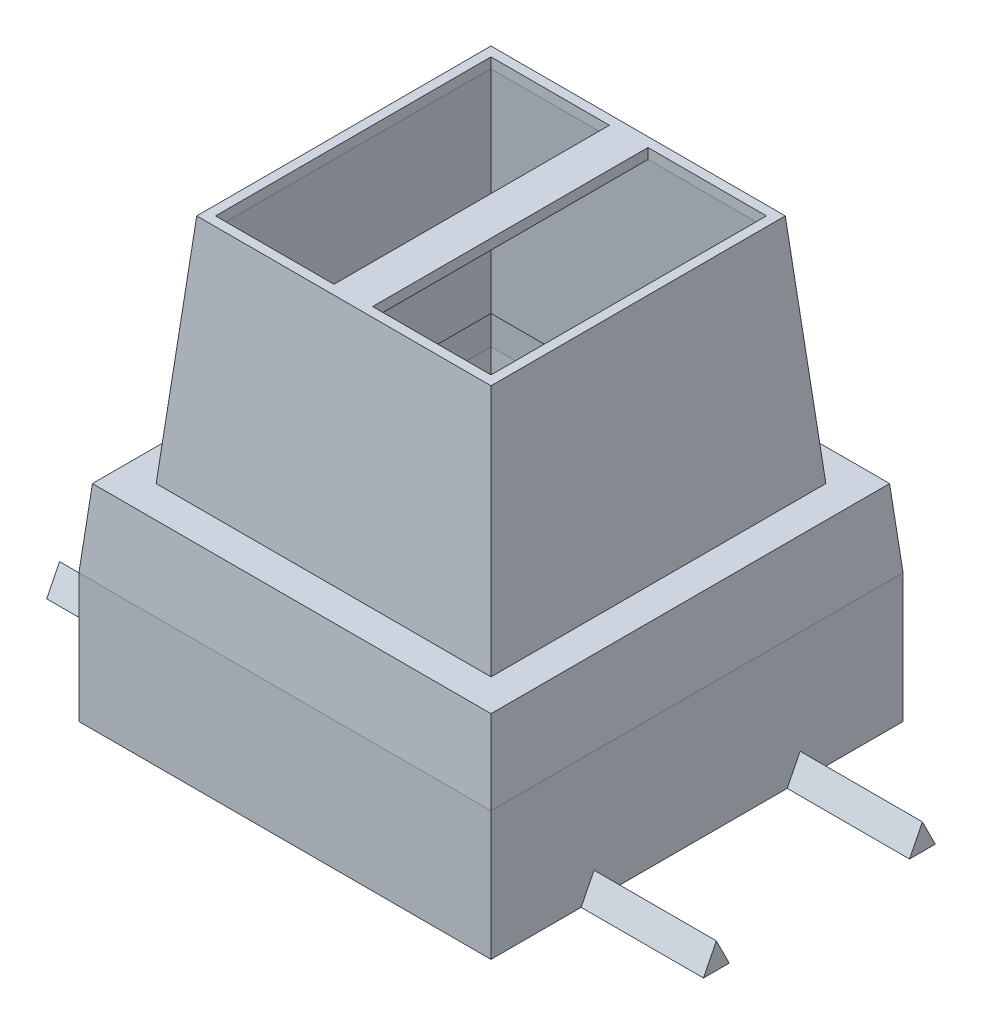
SolidWorks part; units mm, degrees
ref_plane "Front Plane" through (0, 0, 0) normal (0, 0, 1) x (1, 0, 0)
ref_plane "Top Plane" through (0, 0, 0) normal (0, 1, 0) x (1, 0, 0)
ref_plane "Right Plane" through (0, 0, 0) normal (1, 0, 0) x (0, 0, -1)
sketch "Sketch1" plane through (0, 0, 0) normal (0, 1, 0) x (1, 0, 0)
  line L13 (0, 0) -> (-32, 0)
  line L14 (0, 0) -> (0, 32)
  line L15 (0, 32) -> (-32, 32)
  line L16 (-32, 0) -> (-32, 32)
  dimension "D1" = 32
  dimension "D2" = 32
extrude "Boss-Extrude1" add sketch "Sketch1" along normal blind 6 draft 5
sketch "Sketch2" plane through (0, 6, 0) normal (0, 1, 0) x (1, 0, 0)
  line L0 (-31.4751, 0.5249) -> (-0.5249, 0.5249) construction
  line L1 (-29, 29) -> (-3, 29)
  line L2 (-29, 29) -> (-29, 3)
  line L3 (-29, 3) -> (-3, 3)
  line L4 (-3, 29) -> (-3, 3)
  line L5 (-0.5249, 0.5249) -> (-0.5249, 31.4751) construction
  point P5 (-16, 3)
  point P8 (-16, 0.5249)
  point P9 (-3, 16)
  point P12 (-0.5249, 16)
  dimension "D1" = 26
  dimension "D2" = 26
extrude "Boss-Extrude2" add sketch "Sketch2" along normal blind 18 draft 5
shell "Shell1" thickness 0.8 removed face at (-16, 0, -16)
chamfer "Chamfer1" distance 2.5 angle 45 4 edges at (-16, 5.2, -1.258) (-30.742, 5.2, -16) (-16, 5.2, -30.742) (-1.258, 5.2, -16) first distance on face at (-16, 5.2, -16)
sketch "Sketch3" plane through (0, 23.2, 0) normal (0, -1, 0) x (1, 0, 0)
  line L0 (-5.3079, -26.6921) -> (-26.6921, -26.6921) construction
  line L1 (-17.5, -5.3079) -> (-14.5, -5.3079)
  line L2 (-17.5, -5.3079) -> (-17.5, -26.6921)
  line L3 (-17.5, -26.6921) -> (-14.5, -26.6921)
  line L4 (-14.5, -5.3079) -> (-14.5, -26.6921)
  line L5 (-26.6921, -5.3079) -> (-5.3079, -5.3079) construction
  line L7 (-17.5, -5.3079) -> (-26.6921, -5.3079)
  line L8 (-17.5, -5.3079) -> (-17.5, -26.6921)
  line L9 (-17.5, -26.6921) -> (-26.6921, -26.6921)
  line L10 (-26.6921, -5.3079) -> (-26.6921, -26.6921)
  line L11 (-14.5, -5.3079) -> (-5.3079, -5.3079)
  line L12 (-14.5, -5.3079) -> (-14.5, -26.6921)
  line L13 (-14.5, -26.6921) -> (-5.3079, -26.6921)
  line L14 (-5.3079, -5.3079) -> (-5.3079, -26.6921)
  point P6 (-16, -5.3079)
  point P9 (-16, -5.3079)
  line M13 (-26.6921, -5.3079) -> (-26.6921, -26.6921)
  line M14 (-26.6921, -26.6921) -> (-5.3079, -26.6921)
  line M15 (-5.3079, -26.6921) -> (-5.3079, -5.3079)
  line M16 (-5.3079, -5.3079) -> (-26.6921, -5.3079)
  dimension "D1" = 3
extrude "Cut-Extrude1" cut sketch "Sketch3" against normal through all contours L2 M16 M13 M14 | L4 M16 M14 M15 region at (-22.0961, 23.2, -16) region at (-9.9039, 23.2, -16)
sketch "Sketch4" plane through (0, 0, 0) normal (0, -1, 0) x (1, 0, 0)
  line L1 (-32, 0) -> (0, 0)
  line L2 (-32, 0) -> (-32, -32)
  line L3 (-32, -32) -> (0, -32)
  line L4 (0, 0) -> (0, -32)
  line L5 (-0.8031, -31.1969) -> (-31.1969, -31.1969)
  line L6 (-0.8031, -31.1969) -> (-0.8031, -0.8031)
  line L7 (-0.8031, -0.8031) -> (-31.1969, -0.8031)
  line L8 (-31.1969, -31.1969) -> (-31.1969, -0.8031)
extrude "Boss-Extrude3" add sketch "Sketch4" along normal blind 10
sketch "Sketch5" plane through (-32, 0, 0) normal (-1, 0, 0) x (0, 0, 1)
  line L0 (-25, -10) -> (-23, -10)
  line L1 (0, -10) -> (-32, -10) construction
  line L2 (-23, -10) -> (-24, -8)
  line L3 (-24, -8) -> (-25, -10)
  line L4 (-9, -10) -> (-7, -10)
  line L5 (-7, -10) -> (-8, -8)
  line L6 (-8, -8) -> (-9, -10)
  line L7 (-23, -10) -> (-9, -10)
  point P7 (-16, -10)
  point P9 (-24, -10)
  point P10 (-12.8638, -10)
  point P12 (-16, -10)
  point P13 (0, 0)
  point P14 (-12.7902, -10)
  line M10 (-32, -10) -> (0, -10)
  dimension "D1" = 14
  dimension "D2" = 2
  dimension "D3" = 2
extrude "Boss-Extrude4" add sketch "Sketch5" along normal blind 9.5 contours L2 L3 M10 | L5 L6 M10 region at (-32, -9.3333, -24) region at (-32, -9.3333, -8)
extrude "Boss-Extrude5" add sketch "Sketch5<3>" against normal blind 9.5 from surface contours L5 L6 M10 | L2 L3 M10 region at (-32, -9.3333, -24) region at (-32, -9.3333, -8) starting at face at (0, -5, -16)
sketch "Sketch5<3>" plane through (-32, 0, 0) normal (-1, 0, 0) x (0, 0, 1) same geometry as "Sketch5"
equation "\"D2@Sketch1\"=\"D1@Sketch1\""
equation "\"D2@Sketch2\"=\"D1@Sketch2\""
